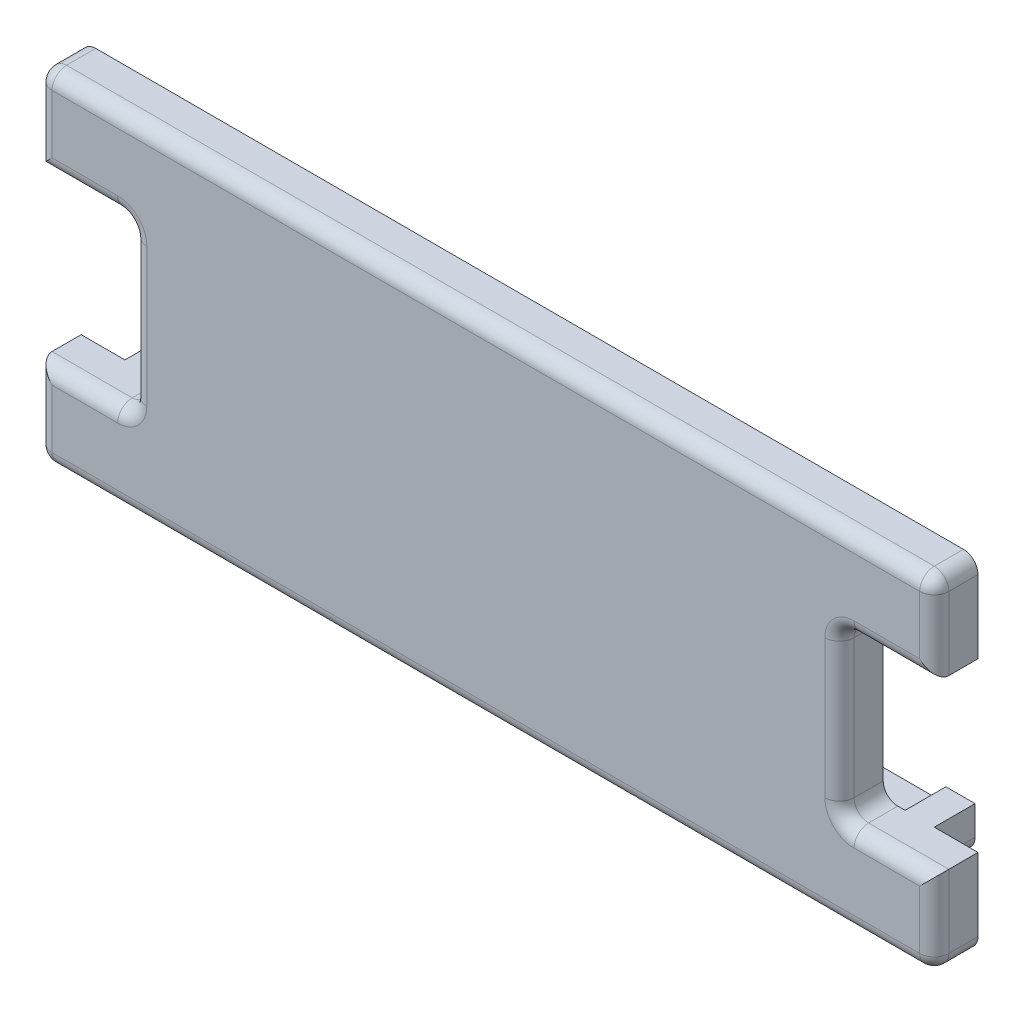
SolidWorks part; units mm, degrees
ref_plane "Front Plane" through (0, 0, 0) normal (0, 0, 1) x (1, 0, 0)
ref_plane "Top Plane" through (0, 0, 0) normal (0, 1, 0) x (1, 0, 0)
ref_plane "Right Plane" through (0, 0, 0) normal (1, 0, 0) x (0, 0, -1)
sketch "Sketch3" plane through (0, 0, 0) normal (0, 0, 1) x (1, 0, 0)
  line L16 (29.75, 11.75) -> (-29.75, 11.75)
  line L17 (-30.75, 10.75) -> (-30.75, 5.75)
  line L18 (-30.75, 5.75) -> (-27.75, 5.75)
  line L19 (-27.75, 5.75) -> (-27.75, 7.75)
  line L20 (-26.75, 8.75) -> (26.75, 8.75)
  line L21 (27.75, 7.75) -> (27.75, 5.75)
  line L22 (27.75, 5.75) -> (30.75, 5.75)
  line L23 (30.75, 5.75) -> (30.75, 10.75)
  line L24 (29.75, 11.75) -> (-29.75, 11.75)
  line L25 (-30.75, 10.75) -> (-30.75, 5.75)
  line L26 (-30.75, 5.75) -> (-27.75, 5.75)
  line L27 (-27.75, 5.75) -> (-27.75, 7.75)
  line L28 (-26.75, 8.75) -> (26.75, 8.75)
  line L29 (27.75, 7.75) -> (27.75, 5.75)
  line L30 (27.75, 5.75) -> (30.75, 5.75)
  line L31 (30.75, 5.75) -> (30.75, 10.75)
  line L32 (-29.75, -13.75) -> (29.75, -13.75)
  line L33 (32.75, -10.75) -> (32.75, -3.75)
  line L34 (32.75, -3.75) -> (25.75, -3.75)
  line L35 (25.75, -3.75) -> (25.75, -6.75)
  line L36 (25.75, -6.75) -> (-25.75, -6.75)
  line L37 (-25.75, -6.75) -> (-25.75, -3.75)
  line L38 (-25.75, -3.75) -> (-32.75, -3.75)
  line L39 (-32.75, -3.75) -> (-32.75, -10.75)
  line L40 (-29.75, -11.75) -> (29.75, -11.75)
  line L41 (30.75, -10.75) -> (30.75, -5.75)
  line L42 (30.75, -5.75) -> (27.75, -5.75)
  line L43 (27.75, -5.75) -> (27.75, -7.75)
  line L44 (26.75, -8.75) -> (-26.75, -8.75)
  line L45 (-27.75, -7.75) -> (-27.75, -5.75)
  line L46 (-27.75, -5.75) -> (-30.75, -5.75)
  line L47 (-30.75, -5.75) -> (-30.75, -10.75)
  line L48 (-29.75, -11.75) -> (29.75, -11.75)
  line L49 (30.75, -10.75) -> (30.75, -5.75)
  line L50 (30.75, -5.75) -> (27.75, -5.75)
  line L51 (27.75, -5.75) -> (27.75, -7.75)
  line L52 (26.75, -8.75) -> (-26.75, -8.75)
  line L53 (-27.75, -7.75) -> (-27.75, -5.75)
  line L54 (-27.75, -5.75) -> (-30.75, -5.75)
  line L55 (-30.75, -5.75) -> (-30.75, -10.75)
  line L56 (29.75, 13.75) -> (-29.75, 13.75)
  line L57 (-32.75, 10.75) -> (-32.75, 3.75)
  line L58 (-32.75, 3.75) -> (-25.75, 3.75)
  line L59 (-25.75, 3.75) -> (-25.75, 6.75)
  line L60 (-25.75, 6.75) -> (25.75, 6.75)
  line L61 (25.75, 6.75) -> (25.75, 3.75)
  line L62 (25.75, 3.75) -> (32.75, 3.75)
  line L63 (32.75, 3.75) -> (32.75, 10.75)
  line L64 (-27.75, 5.75) -> (-25.75, 5.75)
  line L65 (-27.75, -5.75) -> (-25.75, -5.75)
  line L66 (27.75, 5.75) -> (25.75, 5.75)
  line L67 (27.75, -5.75) -> (25.75, -5.75)
  arc A8 (-29.75, 11.75) -> (-30.75, 10.75) centre (-29.75, 10.75) ccw
  arc A9 (-26.75, 8.75) -> (-27.75, 7.75) centre (-26.75, 7.75) ccw
  arc A10 (27.75, 7.75) -> (26.75, 8.75) centre (26.75, 7.75) ccw
  arc A11 (30.75, 10.75) -> (29.75, 11.75) centre (29.75, 10.75) ccw
  arc A12 (-29.75, 11.75) -> (-30.75, 10.75) centre (-29.75, 10.75) ccw
  arc A13 (-26.75, 8.75) -> (-27.75, 7.75) centre (-26.75, 7.75) ccw
  arc A14 (27.75, 7.75) -> (26.75, 8.75) centre (26.75, 7.75) ccw
  arc A15 (30.75, 10.75) -> (29.75, 11.75) centre (29.75, 10.75) ccw
  arc A16 (29.75, -13.75) -> (32.75, -10.75) centre (29.75, -10.75) ccw
  arc A17 (25.75, -6.75) -> (25.75, -6.75) centre (25.75, -6.75) ccw
  arc A18 (-25.75, -6.75) -> (-25.75, -6.75) centre (-25.75, -6.75) ccw
  arc A19 (-32.75, -10.75) -> (-29.75, -13.75) centre (-29.75, -10.75) ccw
  arc A20 (29.75, -11.75) -> (30.75, -10.75) centre (29.75, -10.75) ccw
  arc A21 (26.75, -8.75) -> (27.75, -7.75) centre (26.75, -7.75) ccw
  arc A22 (-27.75, -7.75) -> (-26.75, -8.75) centre (-26.75, -7.75) ccw
  arc A23 (-30.75, -10.75) -> (-29.75, -11.75) centre (-29.75, -10.75) ccw
  arc A24 (29.75, -11.75) -> (30.75, -10.75) centre (29.75, -10.75) ccw
  arc A25 (26.75, -8.75) -> (27.75, -7.75) centre (26.75, -7.75) ccw
  arc A26 (-27.75, -7.75) -> (-26.75, -8.75) centre (-26.75, -7.75) ccw
  arc A27 (-30.75, -10.75) -> (-29.75, -11.75) centre (-29.75, -10.75) ccw
  arc A28 (-29.75, 13.75) -> (-32.75, 10.75) centre (-29.75, 10.75) ccw
  arc A29 (-25.75, 6.75) -> (-25.75, 6.75) centre (-25.75, 6.75) ccw
  arc A30 (25.75, 6.75) -> (25.75, 6.75) centre (25.75, 6.75) ccw
  arc A31 (32.75, 10.75) -> (29.75, 13.75) centre (29.75, 10.75) ccw
  line M29 (-27.75, 5.75) -> (-27.75, 7.75)
  arc M30 (-27.75, 7.75) -> (-26.75, 8.75) centre (-26.75, 7.75) cw
  line M31 (-26.75, 8.75) -> (26.75, 8.75)
  arc M32 (26.75, 8.75) -> (27.75, 7.75) centre (26.75, 7.75) cw
  line M33 (27.75, 7.75) -> (27.75, 5.75)
  dimension "D1" = 0
  dimension "D2" = 0
  dimension "D3" = 2
  dimension "D4" = 2
extrude "Boss-Extrude2" add sketch "Sketch3" against normal blind 2.8 contours L66 L64 L59 L60 L61 M33 M32 M31 M30 M29 | L53 A26 L52 A25 L51 L67 L35 L36 L37 L65 region at (0, 7.6947, 0) region at (0, -7.6947, 0)
sketch "Sketch2" plane through (0, 0, 0) normal (0, 0, 1) x (1, 0, 0)
  line L0 (30.75, -5.75) -> (30.75, 5.75) construction
  line L16 (29.75, 11.75) -> (-29.75, 11.75)
  line L17 (-30.75, 10.75) -> (-30.75, 5.75)
  line L18 (-30.75, 5.75) -> (-27.75, 5.75)
  line L19 (-27.75, 5.75) -> (-27.75, 7.75)
  line L20 (-26.75, 8.75) -> (26.75, 8.75)
  line L21 (27.75, 7.75) -> (27.75, 5.75)
  line L22 (27.75, 5.75) -> (30.75, 5.75)
  line L23 (30.75, 5.75) -> (30.75, 10.75)
  line L24 (29.75, 11.75) -> (-29.75, 11.75)
  line L25 (-30.75, 10.75) -> (-30.75, 5.75)
  line L26 (-30.75, 5.75) -> (-27.75, 5.75)
  line L27 (-27.75, 5.75) -> (-27.75, 7.75)
  line L28 (-26.75, 8.75) -> (26.75, 8.75)
  line L29 (27.75, 7.75) -> (27.75, 5.75)
  line L30 (27.75, 5.75) -> (30.75, 5.75)
  line L31 (30.75, 5.75) -> (30.75, 10.75)
  line L32 (-30.75, 5.75) -> (-24.25, 5.75)
  line L33 (-24.25, 5.75) -> (-24.25, -5.75)
  line L34 (-24.25, -5.75) -> (-27.75, -5.75)
  line L35 (27.75, 5.75) -> (24.25, 5.75)
  line L36 (24.25, 5.75) -> (24.25, -5.75)
  line L37 (24.25, -5.75) -> (27.75, -5.75)
  line L40 (-29.75, -11.75) -> (29.75, -11.75)
  line L41 (30.75, -10.75) -> (30.75, -5.75)
  line L42 (30.75, -5.75) -> (27.75, -5.75)
  line L43 (27.75, -5.75) -> (27.75, -7.75)
  line L44 (26.75, -8.75) -> (-26.75, -8.75)
  line L45 (-27.75, -7.75) -> (-27.75, -5.75)
  line L46 (-27.75, -5.75) -> (-30.75, -5.75)
  line L47 (-30.75, -5.75) -> (-30.75, -10.75)
  line L48 (-29.75, -11.75) -> (29.75, -11.75)
  line L49 (30.75, -10.75) -> (30.75, -5.75)
  line L50 (30.75, -5.75) -> (27.75, -5.75)
  line L51 (27.75, -5.75) -> (27.75, -7.75)
  line L52 (26.75, -8.75) -> (-26.75, -8.75)
  line L53 (-27.75, -7.75) -> (-27.75, -5.75)
  line L54 (-27.75, -5.75) -> (-30.75, -5.75)
  line L55 (-30.75, -5.75) -> (-30.75, -10.75)
  arc A8 (-29.75, 11.75) -> (-30.75, 10.75) centre (-29.75, 10.75) ccw
  arc A9 (-26.75, 8.75) -> (-27.75, 7.75) centre (-26.75, 7.75) ccw
  arc A10 (27.75, 7.75) -> (26.75, 8.75) centre (26.75, 7.75) ccw
  arc A11 (30.75, 10.75) -> (29.75, 11.75) centre (29.75, 10.75) ccw
  arc A12 (-29.75, 11.75) -> (-30.75, 10.75) centre (-29.75, 10.75) ccw
  arc A13 (-26.75, 8.75) -> (-27.75, 7.75) centre (-26.75, 7.75) ccw
  arc A14 (27.75, 7.75) -> (26.75, 8.75) centre (26.75, 7.75) ccw
  arc A15 (30.75, 10.75) -> (29.75, 11.75) centre (29.75, 10.75) ccw
  arc A20 (29.75, -11.75) -> (30.75, -10.75) centre (29.75, -10.75) ccw
  arc A21 (26.75, -8.75) -> (27.75, -7.75) centre (26.75, -7.75) ccw
  arc A22 (-27.75, -7.75) -> (-26.75, -8.75) centre (-26.75, -7.75) ccw
  arc A23 (-30.75, -10.75) -> (-29.75, -11.75) centre (-29.75, -10.75) ccw
  arc A24 (29.75, -11.75) -> (30.75, -10.75) centre (29.75, -10.75) ccw
  arc A25 (26.75, -8.75) -> (27.75, -7.75) centre (26.75, -7.75) ccw
  arc A26 (-27.75, -7.75) -> (-26.75, -8.75) centre (-26.75, -7.75) ccw
  arc A27 (-30.75, -10.75) -> (-29.75, -11.75) centre (-29.75, -10.75) ccw
  line M27 (29.75, 11.75) -> (-29.75, 11.75)
  arc M28 (-29.75, 11.75) -> (-30.75, 10.75) centre (-29.75, 10.75) ccw
  line M29 (-30.75, 10.75) -> (-30.75, 5.75)
  line M30 (-30.75, 5.75) -> (-27.75, 5.75)
  line M31 (-27.75, 5.75) -> (-27.75, 7.75)
  arc M32 (-27.75, 7.75) -> (-26.75, 8.75) centre (-26.75, 7.75) cw
  line M33 (-26.75, 8.75) -> (26.75, 8.75)
  arc M34 (26.75, 8.75) -> (27.75, 7.75) centre (26.75, 7.75) cw
  line M35 (27.75, 7.75) -> (27.75, 5.75)
  line M36 (27.75, 5.75) -> (30.75, 5.75)
  line M37 (30.75, 5.75) -> (30.75, 10.75)
  arc M38 (30.75, 10.75) -> (29.75, 11.75) centre (29.75, 10.75) ccw
  dimension "D3" = 6.5
  dimension "D4" = 6.5
  dimension "D1" = 0
  dimension "D2" = 0
extrude "Boss-Extrude1" add sketch "Sketch2" along normal blind 3 contours L53 A26 L52 A25 L51 L37 L36 L35 L32 L33 L34 M35 M34 M33 M32 M31 | M38 M27 M28 M29 M30 M31 M32 M33 M34 M35 M36 M37 | L55 A27 L48 A24 L49 L50 L51 A25 L52 A26 L53 L54 region at (0, 9.977, 0) region at (0, 0, 0) region at (0, -9.977, 0)
fillet "Fillet1" radius 1 22 edges at (24.25, -5.75, 1.5) (24.25, 5.75, 1.5) (-24.25, -5.75, 1.5) (-24.25, 5.75, 1.5) (-24.25, 0, 3) (-27.5, 5.75, 3) (-30.75, 8.25, 3) (-30.4571, 11.4571, 3) (0, 11.75, 3) (30.4571, 11.4571, 3) (30.75, 8.25, 3) (27.5, 5.75, 3) (24.25, 0, 3) (27.5, -5.75, 3) (30.75, -8.25, 3) (30.4571, -11.4571, 3) (0, -11.75, 3) (-30.4571, -11.4571, 3) (-30.75, -8.25, 3) (-27.5, -5.75, 3) (0, 6.75, 0) (0, -6.75, 0)
